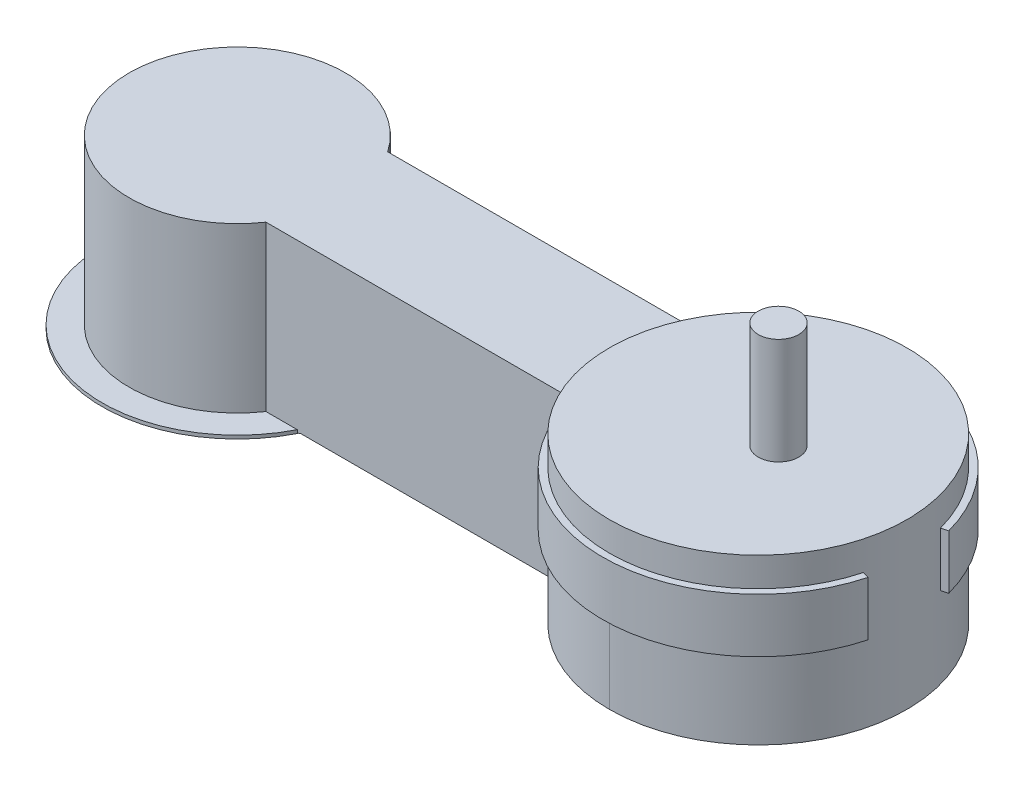
SolidWorks part; units mm, degrees
ref_plane "Front Plane" through (0, 0, 0) normal (0, 0, 1) x (1, 0, 0)
ref_plane "Top Plane" through (0, 0, 0) normal (0, 1, 0) x (1, 0, 0)
ref_plane "Right Plane" through (0, 0, 0) normal (1, 0, 0) x (0, 0, -1)
sketch "Sketch1" plane through (0, 0, 0) normal (0, 1, 0) x (1, 0, 0)
  line L0 (101.7992, 28.575) -> (-84.9987, 28.575)
  line L3 (-84.9987, -28.575) -> (101.7992, -28.575)
  arc A0 (101.7992, -28.575) -> (101.7992, 28.575) centre (127, 0) ccw
  arc A1 (-84.9987, -28.575) -> (-84.9987, 28.575) centre (-127, 0) cw
  dimension "D4" = 38.1
  dimension "D6" = 50.8
  dimension "D1" = 57.15
  dimension "D2" = 28.575
  dimension "D3" = 127
  dimension "D5" = 127
extrude "Boss-Extrude1" add sketch "Sketch1" along normal blind 1.5875
sketch "Sketch2" plane through (0, 1.5875, 0) normal (0, 1, 0) x (1, 0, 0)
  circle A0 centre (-127, 0) radius 9.525
  circle A1 centre (127, 0) radius 9.525
  dimension "D1" = 19.05
  dimension "D2" = 19.05
extrude "Boss-Extrude2" add sketch "Sketch2" along normal blind 76.2 and the other way blind 39.624 contours A0
sketch "Sketch4" plane through (0, 1.5875, 0) normal (0, 1, 0) x (1, 0, 0)
  circle A0 centre (127, 0) radius 9.525
  dimension "D1" = 19.05
extrude "Boss-Extrude3" add sketch "Sketch4" along normal blind 127 and the other way blind 28.575
ref_plane "Plane1" through (0, 76.2, 0) normal (0, 1, 0) x (1, 0, 0)
sketch "Sketch5" plane through (0, 76.2, 0) normal (0, 1, 0) x (1, 0, 0)
  line L0 (-91.6432, 0) -> (91.6432, 0) construction
  circle A0 centre (127, 0) radius 9.525 construction
  circle A1 centre (127, 0) radius 9.525 construction
  circle A4 centre (117.475, 0) radius 69.85
  circle A5 centre (117.475, 0) radius 63.5
  dimension "D1" = 139.7
  dimension "D2" = 9.525
  dimension "D3" = 127
extrude "Boss-Extrude4" add sketch "Sketch5" against normal up to surface (74.6125 mm away) up to face at (127, 1.5875, -9.525)
sketch "Sketch6" plane through (0, 76.2, 0) normal (0, 1, 0) x (1, 0, 0)
  circle A0 centre (117.475, 0) radius 69.85 construction
  circle A4 centre (117.475, 0) radius 69.85
  point P0 (117.475, 0)
extrude "Boss-Extrude5" add sketch "Sketch6" along normal blind 2.54
sketch "Sketch10" plane through (0, 0, 0) normal (0, -1, 0) x (1, 0, 0)
  line L2 (-84.9987, -28.575) -> (101.7992, -28.575)
  line L3 (101.7992, 28.575) -> (-84.9987, 28.575)
  line L4 (60.7677, -28.575) -> (101.7992, -28.575)
  line L5 (101.7992, 28.575) -> (60.7677, 28.575)
  arc A2 (-84.9987, 28.575) -> (-84.9987, -28.575) centre (-127, 0) ccw
  arc A3 (101.7992, -28.575) -> (101.7992, 28.575) centre (127, 0) ccw
  arc A5 (101.7992, -28.575) -> (101.7992, 28.575) centre (127, 0) ccw
  circle A6 centre (127, 0) radius 9.525 construction
  circle A7 centre (127, 0) radius 9.525
  arc A8 (60.7677, 28.575) -> (60.7677, -28.575) centre (117.475, 0) ccw construction
  arc A9 (60.7677, 28.575) -> (60.7677, -28.575) centre (117.475, 0) ccw
  dimension "D1" = 0
extrude "Cut-Extrude3" cut sketch "Sketch10" against normal up to next
ref_plane "Plane2" through (0, 1.5875, 0) normal (0, -1, 0) x (-1, 0, 0)
sketch "Sketch11" plane through (0, 1.5875, 0) normal (0, -1, 0) x (-1, 0, 0)
  circle A0 centre (-127, 0) radius 9.525 construction
  circle A1 centre (-127, 0) radius 9.525
  circle A2 centre (-127, 0) radius 31.75
  dimension "D1" = 63.5
extrude "Boss-Extrude6" add sketch "Sketch11" along normal blind 1.5875
sketch "Sketch13" plane through (0, 1.5875, 0) normal (0, 1, 0) x (1, 0, 0)
  line L0 (-84.9987, -28.575) -> (53.7373, -28.575) construction
  line L1 (53.7373, 28.575) -> (-84.9987, 28.575) construction
  line L2 (-84.9987, -28.575) -> (53.7373, -28.575)
  line L3 (53.7373, 28.575) -> (-84.9987, 28.575)
  line L6 (-86.365, -26.035) -> (49.9288, -26.035)
  line L7 (49.9288, 26.035) -> (-86.365, 26.035)
  arc A1 (-84.9987, 28.575) -> (-84.9987, -28.575) centre (-127, 0) ccw construction
  arc A3 (-84.9987, 28.575) -> (-84.9987, -28.575) centre (-127, 0) ccw
  arc A6 (-86.365, 26.035) -> (-86.365, -26.035) centre (-127, 0) ccw
  arc A7 (53.7373, 28.575) -> (53.7373, -28.575) centre (117.475, 0) ccw construction
  arc A8 (53.7373, 28.575) -> (53.7373, -28.575) centre (117.475, 0) ccw
  arc A9 (49.9288, 26.035) -> (49.9288, -26.035) centre (117.475, 0) ccw
  dimension "D1" = 2.54
extrude "Boss-Extrude7" add sketch "Sketch13" along normal blind 76.2
sketch "Sketch14" plane through (0, 77.7875, 0) normal (0, 1, 0) x (1, 0, 0)
  line L4 (-86.365, -26.035) -> (49.9288, -26.035) construction
  line L5 (49.9288, 26.035) -> (-86.365, 26.035) construction
  line L6 (-86.365, -26.035) -> (49.9288, -26.035)
  line L7 (49.9288, 26.035) -> (-86.365, 26.035)
  arc A5 (49.9288, 26.035) -> (49.9288, -26.035) centre (117.475, 0) ccw construction
  arc A6 (-86.365, 26.035) -> (-86.365, -26.035) centre (-127, 0) ccw construction
  arc A7 (49.9288, 26.035) -> (49.9288, -26.035) centre (117.475, 0) ccw
  arc A8 (-86.365, 26.035) -> (-86.365, -26.035) centre (-127, 0) ccw
extrude "Boss-Extrude8" add sketch "Sketch14" against normal blind 1.5875
ref_plane "Plane3" through (0, 39.6875, 0) normal (0, -1, 0) x (-1, 0, 0)
sketch "Sketch18" plane through (0, 39.6875, 0) normal (0, -1, 0) x (-1, 0, 0)
  line L0 (84.9987, -28.575) -> (-60.7677, -28.575) construction
  line L1 (-53.7373, 28.575) -> (-50.2729, 28.575)
  line L2 (-53.7373, -28.575) -> (-50.2729, -28.575)
  line L3 (-117.475, 0) -> (-207.3436, 24.0802) construction
  line L4 (-117.475, 0) -> (-221.0608, -27.7557) construction
  line L5 (-117.475, 0) -> (-234.0175, 0) construction
  line L6 (-188.0117, 18.9003) -> (-184.9449, 18.0785)
  line L7 (-188.0117, -18.9003) -> (-184.9449, -18.0785)
  arc A3 (-50.2729, 28.575) -> (-188.0117, 18.9003) centre (-117.475, 0) ccw
  arc A4 (-53.7373, 28.575) -> (-184.9449, 18.0785) centre (-117.475, 0) ccw
  arc A5 (-188.0117, -18.9003) -> (-50.2729, -28.575) centre (-117.475, 0) ccw
  arc A6 (-184.9449, -18.0785) -> (-53.7373, -28.575) centre (-117.475, 0) ccw
  dimension "D1" = 73.025
  dimension "D2" = 15
  dimension "D3" = 30
  dimension "D4" = 117.475
extrude "Boss-Extrude9" add sketch "Sketch18" against normal blind 25.4
sketch "Sketch19" plane through (0, 0, 0) normal (0, -1, 0) x (1, 0, 0)
  circle A0 centre (-127, 0) radius 63.5
  dimension "D1" = 127
extrude "Boss-Extrude10" add sketch "Sketch19" along normal mid plane 1.5875
fillet "Fillet1" radius 2.54 1 edges at (-63.5, 0, 0)
